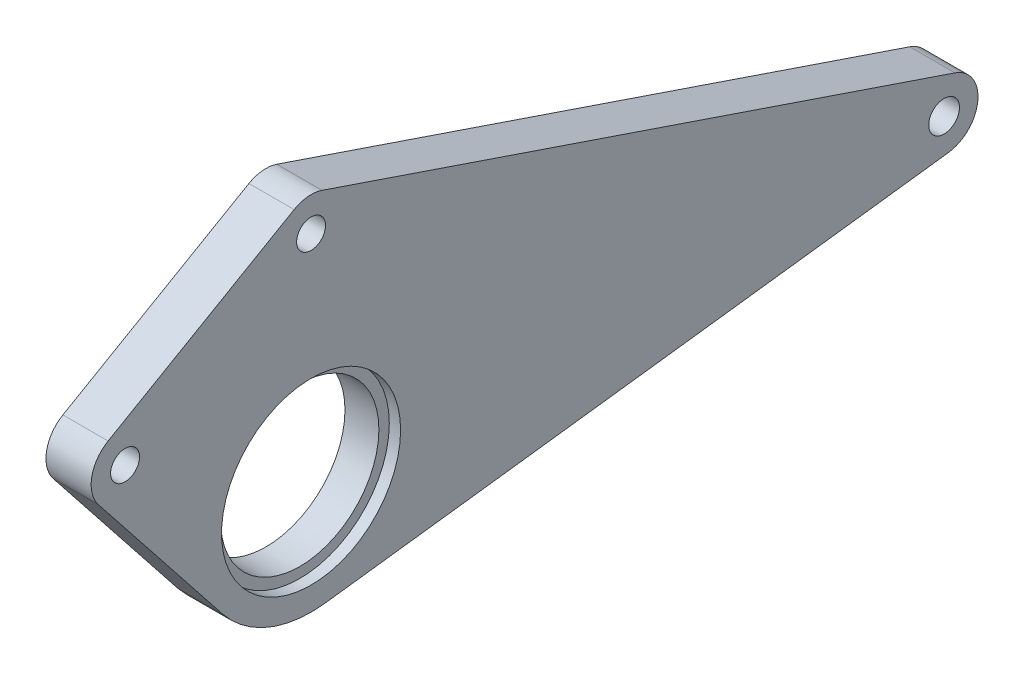
SolidWorks part; units mm, degrees
ref_plane "Front Plane" through (0, 0, 0) normal (0, 0, 1) x (1, 0, 0)
ref_plane "Top Plane" through (0, 0, 0) normal (0, 1, 0) x (1, 0, 0)
ref_plane "Right Plane" through (0, 0, 0) normal (1, 0, 0) x (0, 0, -1)
sketch "Sketch1" plane through (0, 0, 0) normal (1, 0, 0) x (0, 0, -1)
  line L0 (1.5302, 4.51) -> (-87.3698, 34.6725)
  line L1 (-91.2812, 34.2869) -> (-117.4027, 19.2057)
  line L2 (-118.7548, 12.1242) -> (-101.3443, -9.8568)
  line L3 (-86.9156, -15.7505) -> (0.5953, -4.7251)
  line L4 (-115.0215, 15.0813) -> (-88.9, 0) construction
  line L5 (-88.9, 0) -> (-88.9, 30.1625) construction
  line L6 (0, 0) -> (-88.9, 0) construction
  circle A0 centre (0, 0) radius 2.159
  arc A1 (0.5953, -4.7251) -> (1.5302, 4.51) centre (0, 0) ccw
  arc A2 (-87.3698, 34.6725) -> (-91.2812, 34.2869) centre (-88.9, 30.1625) ccw
  arc A3 (-117.4027, 19.2057) -> (-118.7548, 12.1242) centre (-115.0215, 15.0813) ccw
  arc A4 (-101.3443, -9.8568) -> (-86.9156, -15.7505) centre (-88.9, 0) ccw
  circle A5 centre (-88.9, 0) radius 11.1125
  circle A6 centre (-88.9, 30.1625) radius 2.032
  circle A7 centre (-88.9, 0) radius 25.4 construction
  circle A8 centre (-115.0215, 15.0813) radius 2.032
  dimension "D1" = 4.318
  dimension "D2" = 9.525
  dimension "D3" = 22.225
  dimension "D4" = 4.7625
  dimension "D5" = 15.875
  dimension "D6" = 50.8
  dimension "D10" = 4.064
  dimension "D7" = 30.1625
  dimension "D8" = 88.9
  dimension "D9" = 60
extrude "Boss-Extrude1" add sketch "Sketch1" along normal blind 6.35
sketch "Sketch2" plane through (6.35, 0, 0) normal (1, 0, 0) x (0, 0, -1)
  circle A0 centre (-88.9, 0) radius 12.573
  dimension "D1" = 25.146
extrude "Cut-Extrude1" cut sketch "Sketch2" against normal blind 1.5875
mirror "Mirror1" [suppressed] of bodies 102
delete or keep bodies "Body-Delete/Keep 1" [suppressed] type delete bodies bodies 102
